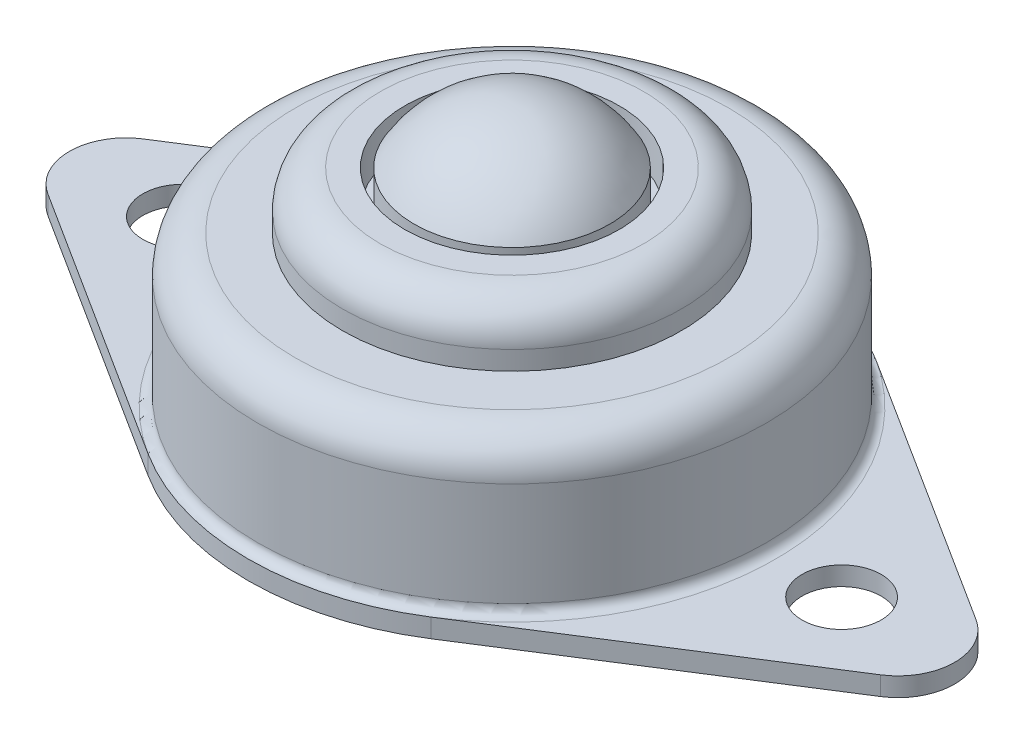
SolidWorks part; units mm, degrees
material "镀铬不锈钢"
ref_plane "前视基准面" through (0, 0, 0) normal (0, 0, 1) x (1, 0, 0)
ref_plane "上视基准面" through (0, 0, 0) normal (0, 1, 0) x (1, 0, 0)
ref_plane "右视基准面" through (0, 0, 0) normal (1, 0, 0) x (0, 0, -1)
sketch "草图1" plane through (0, 0, 0) normal (0, 1, 0) x (1, 0, 0)
  line L0 (-12.2, 0) -> (60.715, 0) construction
  line L1 (-31.3434, 0) -> (39.2454, 0) construction
  line L2 (0, 30.2793) -> (0, -27.96) construction
  line L3 (-22.1098, 2.5315) -> (-7.5122, 11.8138)
  line L4 (-22.1098, -2.5315) -> (-7.5122, -11.8138)
  line L5 (-23.5, 0) -> (-23.5, 5.5142) construction
  line L6 (22.1098, -2.5315) -> (7.5122, -11.8138)
  line L7 (22.1098, 2.5315) -> (7.5122, 11.8138)
  arc A0 (-7.5122, -11.8138) -> (7.5122, -11.8138) centre (0, 0) ccw
  circle A2 centre (-17.5, 0) radius 2.1
  arc A3 (-22.1098, 2.5315) -> (-22.1098, -2.5315) centre (-20.5, 0) ccw
  circle A4 centre (17.5, 0) radius 2.1
  arc A5 (22.1098, 2.5315) -> (22.1098, -2.5315) centre (20.5, 0) cw
  arc A6 (7.5122, 11.8138) -> (-7.5122, 11.8138) centre (0, 0) ccw
  point P17 (-26.0909, 0)
  dimension "D1" = 28
  dimension "D2" = 23.5
  dimension "D4" = 4.2
  dimension "D5" = 3
  dimension "D3" = 35
extrude "凸台-拉伸1" add sketch "草图1" along normal blind 1
sketch "草图2" plane through (0, 1, 0) normal (0, 1, 0) x (1, 0, 0)
  circle A0 centre (0, 0) radius 13.5
  dimension "D1" = 27
extrude "凸台-拉伸2" add sketch "草图2" along normal blind 11
fillet "圆角1" radius 0.5 1 edges at (0, 1, 13.5)
sketch "草图3" plane through (0, 0, 0) normal (0, 0, 1) x (1, 0, 0)
  line L0 (0, 0.3695) -> (0, 17.6305) construction
  line L1 (0, 15) -> (0, 3)
  line L2 (7.5122, 0) -> (22.1098, 0) construction
  arc A0 (0, 15) -> (0, 3) centre (0, 9) ccw
  dimension "D1" = 6
  dimension "D2" = 9
revolve "旋转1" add sketch "草图3" angle 360 about L0 other way angle 360
sketch "草图4" plane through (0, 12, 0) normal (0, 1, 0) x (1, 0, 0)
  circle A0 centre (0, 0) radius 9
  circle A1 centre (0, 0) radius 13.5
  circle A2 centre (0, 0) radius 13.5
  dimension "D2" = 18
  dimension "D1" = 0
extrude "切除-拉伸1" cut sketch "草图4" against normal blind 3
fillet "圆角2" radius 2 2 edges at (0, 12, 9) (0, 9, 13.5)
sketch "草图5" plane through (0, 12, 0) normal (0, 1, 0) x (1, 0, 0)
  circle A0 centre (0, 0) radius 5.1962 construction
  circle A1 centre (0, 0) radius 5.1962
  circle A2 centre (0, 0) radius 5.6962
  dimension "D1" = 0.5
extrude "切除-拉伸2" cut sketch "草图5" against normal blind 2
